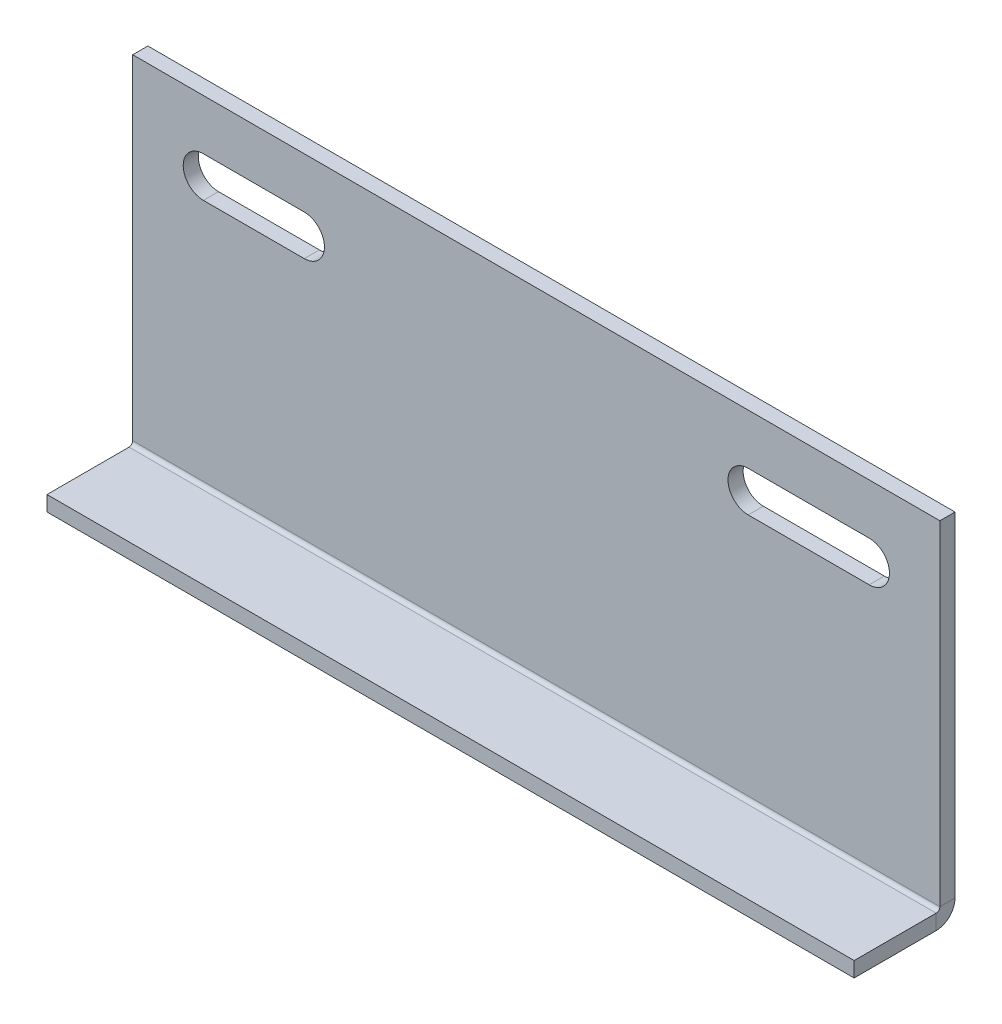
SolidWorks part; units mm, degrees
note: The reader was unsure of these and kept them because the rebuilt part matched: flange length of "Edge-Flange1".
material "Galvanized Steel"
ref_plane "Front Plane" through (0, 0, 0) normal (0, 0, 1) x (1, 0, 0)
ref_plane "Top Plane" through (0, 0, 0) normal (0, 1, 0) x (1, 0, 0)
ref_plane "Right Plane" through (0, 0, 0) normal (1, 0, 0) x (0, 0, -1)
sketch "Sketch2" plane through (0, 0, 0) normal (0, 0, 1) x (1, 0, 0)
  line L0 (-144.6701, 29.1692) -> (-124.6701, 29.1692) construction
  line L1 (1.3299, 43.1692) -> (-158.6701, 43.1692)
  line L2 (1.3299, 43.1692) -> (1.3299, -26.8308)
  line L3 (1.3299, -26.8308) -> (-158.6701, -26.8308)
  line L4 (-158.6701, 43.1692) -> (-158.6701, -26.8308)
  line L5 (-144.6701, 33.1692) -> (-124.6701, 33.1692)
  line L6 (-144.6701, 25.1692) -> (-124.6701, 25.1692)
  line L7 (-12.6701, 29.1692) -> (-36.6701, 29.1692) construction
  line L8 (-12.6701, 25.1692) -> (-36.6701, 25.1692)
  line L9 (-12.6701, 33.1692) -> (-36.6701, 33.1692)
  arc A0 (-144.6701, 33.1692) -> (-144.6701, 25.1692) centre (-144.6701, 29.1692) ccw
  arc A1 (-124.6701, 25.1692) -> (-124.6701, 33.1692) centre (-124.6701, 29.1692) ccw
  arc A2 (-12.6701, 25.1692) -> (-12.6701, 33.1692) centre (-12.6701, 29.1692) ccw
  arc A3 (-36.6701, 33.1692) -> (-36.6701, 25.1692) centre (-36.6701, 29.1692) ccw
  point P6 (-134.6701, 29.1692)
  point P11 (-24.6701, 29.1692)
  point P21 (-120.6701, 29.1692)
  point P22 (-148.6701, 29.1692)
  point P23 (-8.6701, 29.1692)
  dimension "D1" = 160
  dimension "D2" = 70
  dimension "D3" = 14
  dimension "D4" = 14
  dimension "D5" = 28
  dimension "D6" = 8
  dimension "D7" = 28
  dimension "D8" = 8
  dimension "D9" = 14
  dimension "D10" = 14
base flange "Base-Flange1" sketch "Sketch2" thickness 3 reverse thickness direction no parameters "D1"=0.7366
edge flange "Edge-Flange1" sketch "Sketch9" flange angle 90 flange length 20 flange position material inside bend radius 0.7366 thickness 3 relief rectangular parameters "D6"=10
sketch "Sketch9" plane through (0, -26.8308, 0) normal (0, 1, 0) x (-1, 0, 0)
  line L2 (-1.3299, 0) -> (-1.3299, 17)
  line L3 (-1.3299, 17) -> (158.6701, 17)
  line L4 (158.6701, 17) -> (158.6701, 0)
  line L6 (158.6701, 0) -> (-1.3299, 0) construction
  line L7 (158.6701, 0) -> (-1.3299, 0)
bend "EdgeBend1" bend radius 0.7366 bend angle 90 parameters "D5"=1
sketch "Bend-Lines1" [suppressed] plane through (0, 0, 0) normal (0, 1, 0) x (1, 0, 0)
sketch "Bounding-Box1" [suppressed] plane through (0, 0, 0) normal (0, 1, 0) x (1, 0, 0)
sheet metal parameters "Sheet-Metal1" thickness 3 parameters "D1"=0.7366
flat pattern "Flat-Pattern1" [suppressed]
sketch "Bend-Lines2" plane through (0, 0, 0) normal (0, 1, 0) x (1, 0, 0)
sketch3d "Bounding-Box2" [suppressed]
  line L0 (158.6701, -26.8308, 0) -> (-91.3299, -26.8308, 0) construction
  line L1 (158.6701, 43.1692, 0) -> (-91.3299, 43.1692, 0) construction
  line L2 (158.6701, -26.8308, 0) -> (158.6701, 43.1692, 0) construction
  line L3 (-91.3299, -26.8308, 0) -> (-91.3299, 43.1692, 0) construction
sheet metal parameters "Sheet-Metal2" thickness 3 parameters "D1"=0.7366
flat pattern "Flat-Pattern1"
sketch "Bend-Lines2" plane through (0, 0, 0) normal (0, 0, 1) x (1, 0, 0)
  line L0 (-158.6701, -24.8508) -> (1.3299, -24.8508) construction
  line L1 (-158.6701, -24.8508) -> (1.3299, -24.8508) construction
sketch3d "Bounding-Box2" [suppressed]
  line L0 (-158.6701, -42.8708, 0) -> (1.3299, -42.8708, 0) construction
  line L1 (-158.6701, 43.1692, 0) -> (1.3299, 43.1692, 0) construction
  line L2 (-158.6701, -42.8708, 0) -> (-158.6701, 43.1692, 0) construction
  line L3 (1.3299, -42.8708, 0) -> (1.3299, 43.1692, 0) construction
bend of the flat pattern "Flatten-<EdgeBend1>1"
